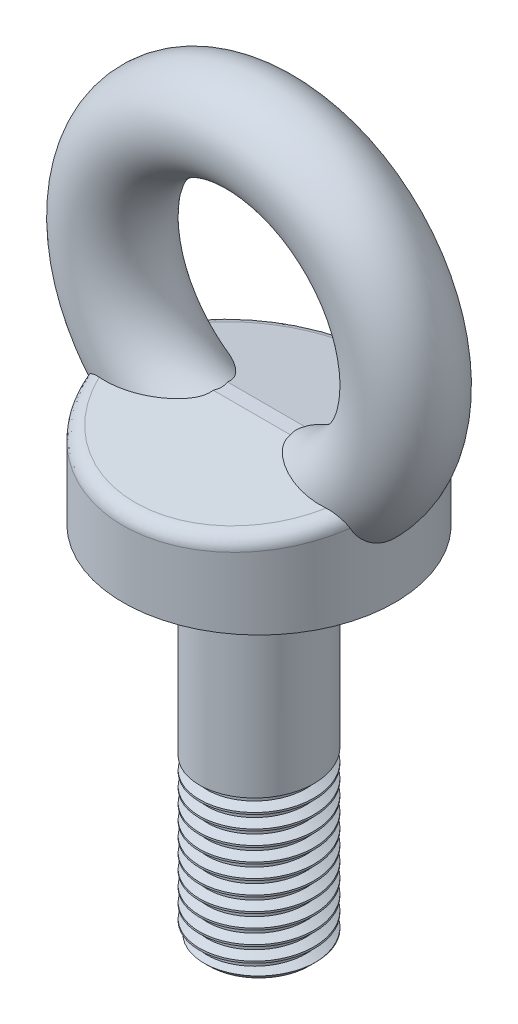
SolidWorks part; units mm, degrees
material "1.0401 (C15)"
ref_plane "Front Plane" through (0, 0, 0) normal (0, 0, 1) x (1, 0, 0)
ref_plane "Top Plane" through (0, 0, 0) normal (0, 1, 0) x (1, 0, 0)
ref_plane "Right Plane" through (0, 0, 0) normal (1, 0, 0) x (0, 0, -1)
sketch "Sketch1" plane through (0, 0, 0) normal (0, 0, 1) x (1, 0, 0)
  line L0 (0, 0) -> (0, 30.5) construction
  line L1 (0, 30.5) -> (-9.5, 30.5)
  line L2 (-9.5, 30.5) -> (-9.5, 25)
  line L3 (-9.5, 25) -> (-4, 25)
  line L6 (-4, 24) -> (-4, 0.5)
  line L7 (-3.5, 0) -> (0, 0)
  line L8 (-4, 0.5) -> (-3.5, 0)
  line L9 (0, 0) -> (0, 30.5)
  line L10 (-4, 24) -> (-4, 25)
  point P9 (-4, 0)
  dimension "D1" = 8
  dimension "D2" = 25
  dimension "D6" = 5.5
  dimension "D7" = 19
revolve "Revolve1" add sketch "Sketch1" angle 360 about L0
sketch "Sketch3" plane through (0, 0, 0) normal (1, 0, 0) x (0, 0, -1)
  line L0 (9.5, 30.5) -> (-9.5, 30.5)
  line L1 (9.5, 30.5) -> (-9.5, 30.5) construction
  line L2 (-9.5, 30.5) -> (-0.5, 32)
  line L3 (-0.5, 32) -> (0.5, 32)
  line L4 (0, 32) -> (0, 30.5) construction
  line L5 (-9.5, 25) -> (9.5, 25) construction
  line L6 (9.5, 30.5) -> (0.5, 32)
  dimension "D1" = 1
  dimension "D2" = 7
extrude "Boss-Extrude1" add sketch "Sketch3" along normal mid plane 30
sketch "Sketch4" plane through (0, 30.5, 0) normal (0, -1, 0) x (1, 0, 0)
  line L12 (-16, -10.5) -> (0, -10.5)
  line L13 (0, -10.5) -> (16, -10.5)
  line L14 (16, -10.5) -> (16, 10.5)
  line L15 (16, 10.5) -> (0, 10.5)
  line L16 (0, 10.5) -> (-16, 10.5)
  line L17 (-16, 10.5) -> (-16, -10.5)
  line L18 (-16, -10.5) -> (0, -10.5)
  line L19 (0, -10.5) -> (16, -10.5)
  line L20 (16, -10.5) -> (16, 10.5)
  line L21 (16, 10.5) -> (0, 10.5)
  line L22 (0, 10.5) -> (-16, 10.5)
  line L23 (-16, 10.5) -> (-16, -10.5)
  circle A0 centre (0, 0) radius 9.5
  dimension "D1" = 1
extrude "Cut-Extrude1" cut sketch "Sketch4" against normal through all
fillet "Fillet1" radius 1 2 edges at (0, 30.5, -9.5) (0, 30.5, 9.5)
thread "Thread1" pitch 1 method cut profile "Thread Profile1" start angle 0, offset 1, length 0, pitch 1, diameter 8
ref_plane "Plane1" through (4, -0.5, 0) normal (0, 0, 1) x (1, 0, 0)
sketch "Thread Profile1" plane through (4, -0.5, 0) normal (0, 0, 1) x (1, 0, 0)
  line L0 (0, 0) -> (0, 1) construction
  line L11 (0, 0) -> (0, 0.875)
  line L12 (0, 0.875) -> (-0.5413, 0.5625)
  line L13 (-0.5413, 0.5625) -> (-0.5413, 0.3125)
  line L15 (-0.5413, 0.3125) -> (0, 0)
  line L17 (-0.5413, 0.4375) -> (0, 0.4375) construction
  point P2 (0, 0)
  dimension "Pitch" = 1
  dimension "Profile_Angle" = 60
  dimension "Profile_Land" = 0.25
  dimension "Profile_Height" = 0.5413
sketch "Sketch8" plane through (0, 0, 0) normal (0, 0, 1) x (1, 0, 0)
  line L0 (-9.5, 25) -> (9.5, 25) construction
  circle A0 centre (0, 38.5) radius 13.5 construction
  circle A1 centre (0, 38.5) radius 10.25
  dimension "D1" = 27
  dimension "D2" = 3.25
sketch "Sketch9" plane through (0, 0, 0) normal (1, 0, 0) x (0, 0, -1)
  line L0 (0, 52) -> (0, 25) construction
  circle A0 centre (0, 28.25) radius 3.25
  dimension "D1" = 6.5
sweep "Sweep1" add profiles "Sketch9" path "Sketch8"
ref_plane "Plane2" through (0, 0, 10) normal (0, 0, 1) x (1, 0, 0)
ref_plane "Plane3" through (0, 0, -10) normal (0, 0, 1) x (1, 0, 0)
